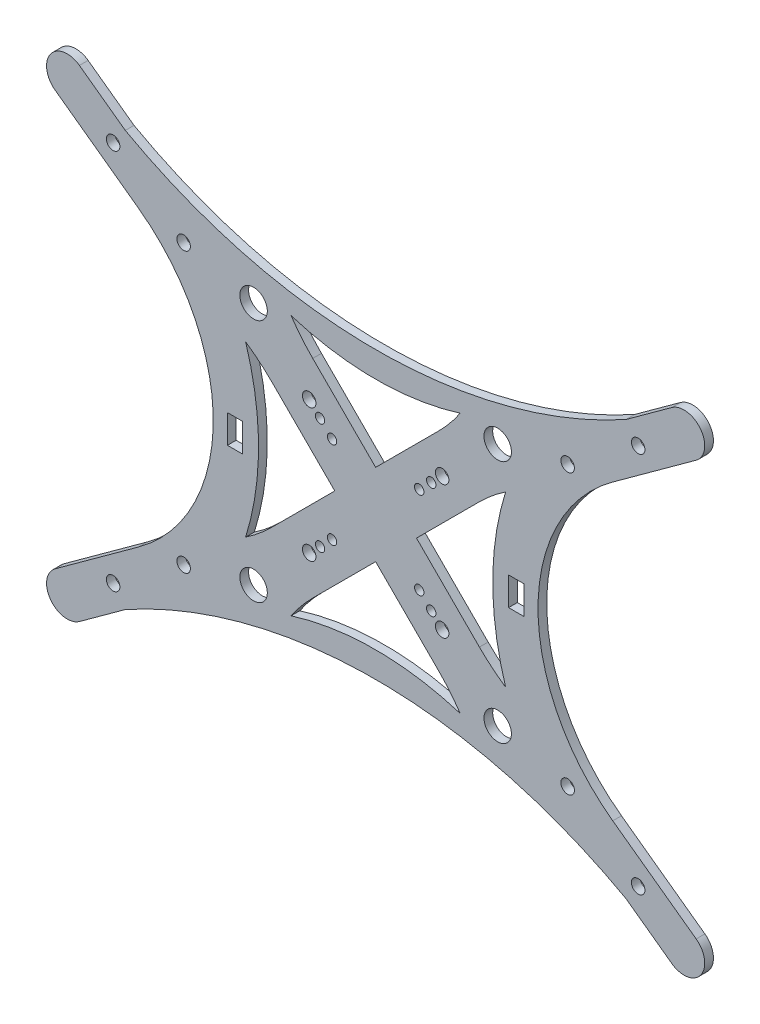
SolidWorks part; units mm, degrees
material "PPS"
ref_plane "前视基准面" through (0, 0, 0) normal (0, 0, 1) x (1, 0, 0)
ref_plane "上视基准面" through (0, 0, 0) normal (0, 1, 0) x (1, 0, 0)
ref_plane "右视基准面" through (0, 0, 0) normal (1, 0, 0) x (0, 0, -1)
sketch "草图7" plane through (0, 0, 0) normal (0, 0, 1) x (1, 0, 0)
  line L0 (-137.4469, 0) -> (193.7386, 0) construction
  line L1 (0, 90.5001) -> (0, -188.7446) construction
  line L2 (0, 0) -> (86.3378, -62.728) construction
  line L61 (-67.9485, -55.2388) -> (-57.4206, -47.5898)
  line L62 (-73.5325, -47.5531) -> (-54.395, -33.649)
  line L66 (-67.9485, 55.2388) -> (-57.4206, 47.5898)
  line L82 (-73.5325, 47.5531) -> (-54.395, 33.649)
  line L93 (73.5325, 47.5531) -> (54.395, 33.649)
  line L94 (-34, -3.25) -> (-34, 3.25) construction
  line L95 (67.9485, 55.2388) -> (57.4206, 47.5898)
  line L104 (15.25, 15.25) -> (0, 0) construction
  line L105 (67.9485, -55.2388) -> (57.4206, -47.5898)
  line L106 (73.5325, -47.5531) -> (54.395, -33.649)
  line L107 (0, 0) -> (86.3378, 62.728) construction
  circle A40 centre (10, 10) radius 1.075
  circle A65 centre (12.75, 12.75) radius 1.075
  circle A66 centre (15.25, 15.25) radius 1.55
  circle A73 centre (15.25, -15.25) radius 1.55
  circle A74 centre (12.75, -12.75) radius 1.075
  circle A75 centre (10, -10) radius 1.075
  circle A76 centre (28, -28) radius 3.15
  circle A89 centre (28, 28) radius 3.15
  arc A132 (67.9485, 55.2388) -> (73.5325, 47.5531) centre (70.7405, 51.396) cw
  arc A133 (54.395, 33.649) -> (54.395, -33.649) centre (78.8424, 0) ccw
  circle A134 centre (60.2246, 43.7557) radius 1.55
  arc A135 (-57.4206, -47.5898) -> (57.4206, -47.5898) centre (0, -151.3241) cw
  circle A136 centre (-60.2246, 43.7557) radius 1.55
  arc A138 (-54.395, 33.649) -> (-54.395, -33.649) centre (-78.8424, 0) cw
  arc A139 (-67.9485, 55.2388) -> (-73.5325, 47.5531) centre (-70.7405, 51.396) ccw
  circle A152 centre (-28, 28) radius 3.15
  circle A153 centre (-28, -28) radius 3.15
  circle A154 centre (-10, -10) radius 1.075
  circle A155 centre (-12.75, -12.75) radius 1.075
  circle A156 centre (-15.25, -15.25) radius 1.55
  circle A157 centre (-15.25, 15.25) radius 1.55
  circle A158 centre (-12.75, 12.75) radius 1.075
  circle A159 centre (-10, 10) radius 1.075
  arc A166 (-57.4206, 47.5898) -> (57.4206, 47.5898) centre (0, 151.3241) ccw
  arc A167 (67.9485, -55.2388) -> (73.5325, -47.5531) centre (70.7405, -51.396) ccw
  arc A172 (-67.9485, -55.2388) -> (-73.5325, -47.5531) centre (-70.7405, -51.396) cw
  circle A176 centre (60.2246, -43.7557) radius 1.55
  circle A177 centre (44.0442, -32) radius 1.55
  circle A178 centre (44.0442, 32) radius 1.55
  circle A179 centre (-44.0442, 32) radius 1.55
  circle A180 centre (-60.2246, -43.7557) radius 1.55
  circle A181 centre (-44.0442, -32) radius 1.55
  point P49 (-37.25, 0)
  dimension "D2" = 2.75
  dimension "D4" = 2.5
  dimension "D1" = 2.15
  dimension "D3" = 3.1
  dimension "D6" = 3.1
  dimension "D10" = 10
  dimension "D5" = 45
  dimension "D7" = 4.75
  dimension "D8" = 3.25
  dimension "D9" = 10
  dimension "D11" = 12.75
  dimension "D16" = 36
sketch "草图8" plane through (0, 0, 0) normal (0, 0, 1) x (1, 0, 0)
  line L0 (-96.7808, 0) -> (86.8563, 0) construction
  line L1 (0, 52.226) -> (0, -62.4511) construction
  line L2 (34, -3.25) -> (30.5, -3.25)
  line L3 (-34, 3.25) -> (-30.5, 3.25)
  line L4 (-34, 3.25) -> (-34, -3.25)
  line L5 (-34, -3.25) -> (-30.5, -3.25)
  line L6 (-30.5, 3.25) -> (-30.5, -3.25)
  line L7 (30.5, 3.25) -> (30.5, -3.25)
  line L8 (34, 3.25) -> (30.5, 3.25)
  line L9 (34, 3.25) -> (34, -3.25)
  dimension "D1" = 30.5
  dimension "D2" = 6.5
  dimension "D3" = 3.5
sketch "草图6" plane through (0, 0, 0) normal (0, 0, 1) x (1, 0, 0)
  line L3 (-23.8014, 14.4296) -> (-9.3719, 0)
  line L9 (-58.8867, 0) -> (57.6096, 0) construction
  line L14 (-23.8014, -14.4296) -> (-9.3719, 0)
  line L15 (0, 29.8455) -> (0, -115.5328) construction
  line L29 (14.4296, 23.8014) -> (0, 9.3719)
  line L30 (-14.4296, 23.8014) -> (0, 9.3719)
  line L31 (23.8014, -14.4296) -> (9.3719, 0)
  line L32 (23.8014, 14.4296) -> (9.3719, 0)
  line L33 (-14.4296, -23.8014) -> (0, -9.3719)
  line L34 (14.4296, -23.8014) -> (0, -9.3719)
  arc A18 (-23.8014, 14.4296) -> (-29.8202, 19.4008) centre (-52.8883, -14.6573) ccw
  arc A19 (-23.8014, -14.4296) -> (-29.8202, -19.4008) centre (-52.8883, 14.6573) cw
  arc A20 (-29.8202, -19.4008) -> (-29.8202, 19.4008) centre (-91.9966, 0) ccw
  arc A33 (-14.4296, 23.8014) -> (-19.4008, 29.8202) centre (14.6573, 52.8883) cw
  arc A34 (-19.4008, 29.8202) -> (19.4008, 29.8202) centre (0, 91.9966) ccw
  arc A35 (14.4296, 23.8014) -> (19.4008, 29.8202) centre (-14.6573, 52.8883) ccw
  arc A36 (23.8014, 14.4296) -> (29.8202, 19.4008) centre (52.8883, -14.6573) cw
  arc A37 (29.8202, 19.4008) -> (29.8202, -19.4008) centre (91.9966, 0) ccw
  arc A38 (23.8014, -14.4296) -> (29.8202, -19.4008) centre (52.8883, 14.6573) ccw
  arc A39 (14.4296, -23.8014) -> (19.4008, -29.8202) centre (-14.6573, -52.8883) cw
  arc A40 (19.4008, -29.8202) -> (-19.4008, -29.8202) centre (0, -91.9966) ccw
  arc A41 (-14.4296, -23.8014) -> (-19.4008, -29.8202) centre (14.6573, -52.8883) ccw
  point P49 (0, 0)
  dimension "D1" = 4
extrude "凸台-拉伸1" add sketch "草图7" along normal blind 2
extrude "切除-拉伸2" cut sketch "草图6" along normal through all
extrude "切除-拉伸3" cut sketch "草图8" along normal through all
